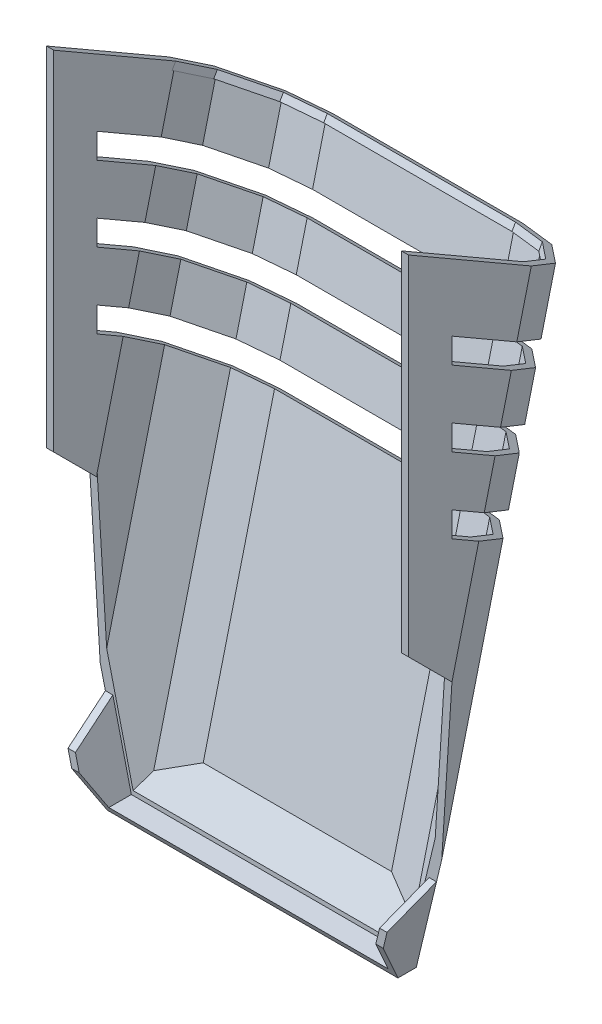
SolidWorks part; units mm, degrees
ref_plane "Plan de face" through (0, 0, 0) normal (0, 0, 1) x (1, 0, 0)
ref_plane "Plan de dessus" through (0, 0, 0) normal (0, 1, 0) x (1, 0, 0)
ref_plane "Plan de droite" through (0, 0, 0) normal (1, 0, 0) x (0, 0, -1)
sketch "Esquisse3" plane through (0, 0, 0) normal (1, 0, 0) x (0, 0, -1)
  line L0 (0, 0) -> (0, 1000)
  line L1 (0, 1000) -> (216.5064, 875)
  line L2 (216.5064, 875) -> (0, 0)
  line L3 (0, 1000) -> (-38.6526, 1022.3161) construction
  dimension "D1" = 120
  dimension "D2" = 1000
  dimension "D3" = 250
extrude "Boss.-Extru.1" add sketch "Esquisse3" along normal blind 500
chamfer "Chanfrein2" distance 80 angle 45 2 edges at (500, 437.5, -108.2532) (0, 437.5, -108.2532)
chamfer "Chanfrein3" distance 20 angle 30 4 edges at (500, 624.8499, -72.1977) (420, 437.5, -108.2532) (0, 624.8499, -72.1977) (80, 437.5, -108.2532)
chamfer "Chanfrein4" distance 190 angle 25 1 edges at (250, 0, 0)
sketch "Esquisse4" plane through (0, 0, 0) normal (0, 0, 1) x (1, 0, 0)
  line L0 (500, 1000) -> (0, 1000)
  line L1 (0, 1000) -> (0, 493.9254)
  line L2 (14.1421, 274.1882) -> (49.2853, 127.8756)
  line L3 (49.2853, 127.8756) -> (450.7147, 127.8756)
  line L4 (450.7147, 127.8756) -> (485.8579, 274.1882)
  line L5 (0, 493.9254) -> (14.1421, 274.1882)
  line L6 (485.8579, 274.1882) -> (500, 493.9254)
  line L7 (500, 493.9254) -> (500, 1000)
extrude "Boss.-Extru.2" add sketch "Esquisse4" along normal blind 60
sketch "Esquisse5" plane through (0, 0, 0) normal (-1, 0, 0) x (0, 0, 1)
  line L0 (60, 1000) -> (60, 1034.641)
  line L1 (60, 1034.641) -> (0, 1000)
  line L2 (0, 1000) -> (60, 1000)
  line L3 (-109.5684, 936.7407) -> (0, 1000) construction
extrude "Boss.-Extru.3" add sketch "Esquisse5" against normal up to surface (500 mm away) up to face at (500, 784.9183, 2.0863)
shell "Coque1" thickness 10
sketch "Esquisse6" plane through (0, 750, -433.0127) normal (0, 0.866, -0.5) x (1, 0, 0)
  line L62 (250, -260) -> (250, -569.282) construction
  line L63 (500, -569.282) -> (0, -569.282) construction
  line L64 (10, -569.282) -> (10, -757.5012)
  line L65 (10, -757.5012) -> (490, -757.5012)
  line L66 (379.9946, -260) -> (428.824, -273.618)
  line L67 (10, -374.7479) -> (10, -569.282)
  line L68 (23.1719, -323.5823) -> (10, -374.7479)
  line L69 (71.176, -273.618) -> (23.1719, -323.5823)
  line L70 (120.0054, -260) -> (71.176, -273.618)
  line L71 (381.363, -260) -> (120.0054, -260)
  line L72 (10, -374.7479) -> (10, -569.282)
  line L73 (23.1719, -323.5823) -> (10, -374.7479)
  line L74 (71.176, -273.618) -> (23.1719, -323.5823)
  line L75 (120.0054, -260) -> (71.176, -273.618)
  line L76 (379.9946, -260) -> (120.0054, -260)
  line L77 (428.824, -273.618) -> (476.8281, -323.5823)
  line L78 (476.8281, -323.5823) -> (490, -374.7479)
  line L79 (490, -374.7479) -> (490, -569.282)
  line L80 (490, -757.5012) -> (490, -569.282)
  line M21 (0, -569.282) -> (500, -569.282)
  dimension "D1" = 10
extrude "Enlèv. mat.-Extru.2" cut sketch "Esquisse6" against normal up to next and the other way through all contours L65 L80 L64 M21 | L76 L62 L79 L78 L77 L66 M21 | L62 L76 L75 L74 L73 L72 M21
sketch "Esquisse7" plane through (0, 0, 60) normal (0, 0, 1) x (1, 0, 0)
  line L0 (250, 416.077) -> (250, 127.8756) construction
  line L1 (379.9946, 416.077) -> (120.0054, 416.077) construction
  line L2 (49.2853, 127.8756) -> (450.7147, 127.8756) construction
  line L3 (450.7147, 127.8756) -> (485.8579, 274.1882) construction
  line L4 (485.8579, 274.1882) -> (500, 493.9254) construction
  line L5 (24.0663, 275.688) -> (475.9337, 275.688) construction
  line L8 (475.9337, 275.688) -> (442.8322, 137.8756)
  line L9 (490, 494.2468) -> (475.9337, 275.688)
  line L10 (490, 1034.641) -> (490, 494.2468)
  line L11 (490, 1034.641) -> (10, 1034.641)
  line L12 (10, 1034.641) -> (10, 494.2468)
  line L13 (10, 494.2468) -> (24.0663, 275.688)
  line L15 (57.1678, 137.8756) -> (450.7147, 137.8756)
  line L16 (10, 1034.641) -> (10, 494.2468)
  line L17 (10, 494.2468) -> (24.0663, 275.688)
  line L19 (57.1678, 137.8756) -> (450.7147, 137.8756) construction
  line L20 (442.8322, 137.8756) -> (57.1678, 137.8756)
  line L23 (24.0663, 275.688) -> (57.1678, 137.8756)
  line L24 (24.0663, 275.688) -> (57.1678, 137.8756)
  dimension "D1" = 10
extrude "Enlèv. mat.-Extru.3" cut sketch "Esquisse7" against normal up to vertex (10 mm away)
sketch "Esquisse8" plane through (500, 0, 0) normal (1, 0, 0) x (0, 0, -1)
  line L0 (-60, 493.9254) -> (0, 493.9254)
  line L1 (0, 493.9254) -> (0, 274.1882)
  line L2 (0, 274.1882) -> (-60, 274.1882) construction
  line L3 (-60, 274.1882) -> (-60, 493.9254)
  line L4 (-60, 274.1882) -> (-60, 244.1882)
  line L5 (-60, 127.8756) -> (-60, 274.1882) construction
  line L6 (-60, 244.1882) -> (0, 244.1882)
  line L7 (0, 127.8756) -> (0, 274.1882) construction
  line L8 (0, 244.1882) -> (0, 274.1882)
  dimension "D1" = 30
extrude "Enlèv. mat.-Extru.4" cut sketch "Esquisse8" against normal through all
chamfer "Chanfrein6" distance 60 angle 30 3 edges at (26.4901, 244.1882, 60) (250, 127.8756, 60) (473.5099, 244.1882, 60)
chamfer "Chanfrein7" distance 60 angle 45 2 edges at (5.0103, 493.9254, 60) (494.9897, 493.9254, 60)
sketch "Esquisse10" plane through (500, 0, 0) normal (1, 0, 0) x (0, 0, -1)
  line L0 (196.5064, 794.171) -> (0, 907.624) construction
  line L1 (216.5064, 875) -> (45.6365, 184.4378) construction
  line L2 (0, 907.624) -> (0, 493.9254) construction
  line L3 (0, 493.9254) -> (106.938, 432.1847) construction
  line L6 (157.1429, 909.2735) -> (203.7588, 882.3598) construction
  line L7 (196.5064, 794.171) -> (0, 907.624)
  line L8 (0, 907.624) -> (0, 872.9829)
  line L9 (0, 872.9829) -> (189.0064, 763.8601)
  line L10 (189.0064, 763.8601) -> (196.5064, 794.171)
  line L11 (174.0064, 703.2383) -> (0, 803.7009)
  line L12 (0, 803.7009) -> (0, 769.0599)
  line L13 (0, 769.0599) -> (166.5064, 672.9274)
  line L14 (166.5064, 672.9274) -> (174.0064, 703.2383)
  line L15 (151.5064, 612.3056) -> (0, 699.7779)
  line L16 (0, 699.7779) -> (0, 665.1368)
  line L17 (0, 665.1368) -> (144.0064, 581.9947)
  line L18 (144.0064, 581.9947) -> (151.5064, 612.3056)
  dimension "D1" = 80
  dimension "D2" = 30
  dimension "D3" = 60
  dimension "D4" = 30
  dimension "D5" = 60
  dimension "D6" = 30
extrude "Enlèv. mat.-Extru.5" cut sketch "Esquisse10" against normal through all
